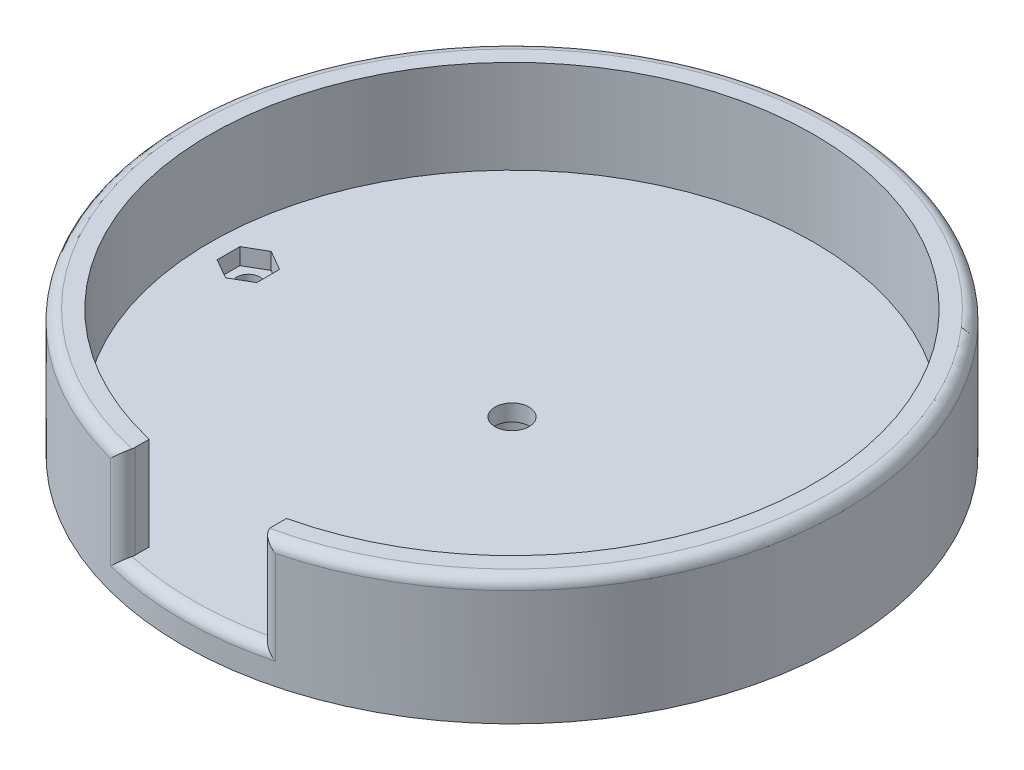
SolidWorks part; units mm, degrees
material "PLA"
ref_plane "Front Plane" through (0, 0, 0) normal (0, 0, 1) x (1, 0, 0)
ref_plane "Top Plane" through (0, 0, 0) normal (0, 1, 0) x (1, 0, 0)
ref_plane "Right Plane" through (0, 0, 0) normal (1, 0, 0) x (0, 0, -1)
sketch "Sketch1" plane through (0, 0, 0) normal (0, 1, 0) x (1, 0, 0)
  line L0 (0, 0) -> (0, -31618.1629) construction
  circle A0 centre (0, 0) radius 60
  circle A1 centre (-48, 0) radius 2.1
  circle A2 centre (0, 0) radius 3.1
  circle A3 centre (48, 0) radius 2.1
  point P6 (0, 0)
  dimension "D1" = 6.2
  dimension "D2" = 4.2
  dimension "D4" = 120
  dimension "D3" = 48
extrude "Boss-Extrude1" add sketch "Sketch1" along normal blind 6
sketch "Sketch2" plane through (0, 6, 0) normal (0, 1, 0) x (1, 0, 0)
  line L0 (0, 0) -> (0, 50000) construction
  line L1 (-51.6, 2.0785) -> (-51.6, -2.0785)
  line L2 (-51.6, -2.0785) -> (-48, -4.1569)
  line L3 (-48, -4.1569) -> (-44.4, -2.0785)
  line L4 (-44.4, -2.0785) -> (-44.4, 2.0785)
  line L5 (-44.4, 2.0785) -> (-48, 4.1569)
  line L6 (-48, 4.1569) -> (-51.6, 2.0785)
  line L7 (48, 4.1569) -> (51.6, 2.0785)
  line L8 (44.4, 2.0785) -> (48, 4.1569)
  line L9 (44.4, -2.0785) -> (44.4, 2.0785)
  line L10 (48, -4.1569) -> (44.4, -2.0785)
  line L11 (51.6, -2.0785) -> (48, -4.1569)
  line L12 (51.6, 2.0785) -> (51.6, -2.0785)
  circle A0 centre (-48, 0) radius 3.6 construction
  circle A1 centre (48, 0) radius 3.6 construction
  point P1 (-51.6, 0)
  dimension "D1" = 7.2
extrude "Cut-Extrude1" cut sketch "Sketch2" against normal blind 3
sketch "Sketch3" plane through (0, 0, 0) normal (0, -1, 0) x (1, 0, 0)
  circle A0 centre (0, 0) radius 4.8
  dimension "D1" = 9.6
extrude "Cut-Extrude2" cut sketch "Sketch3" against normal blind 3
sketch "Sketch4" plane through (0, 6, 0) normal (0, 1, 0) x (1, 0, 0)
  circle A0 centre (0, 0) radius 60
  circle A1 centre (0, 0) radius 55
  dimension "D1" = 120
  dimension "D2" = 5
extrude "Boss-Extrude2" add sketch "Sketch4" along normal blind 17
sketch "Sketch5" plane through (0, 6, 0) normal (0, 1, 0) x (1, 0, 0)
  line L1 (12.5, -67.5) -> (-12.5, -67.5)
  line L2 (12.5, -67.5) -> (12.5, -32.5)
  line L3 (12.5, -32.5) -> (-12.5, -32.5)
  line L4 (-12.5, -67.5) -> (-12.5, -32.5)
  line L5 (12.5, -67.5) -> (-12.5, -32.5) construction
  line L6 (12.5, -32.5) -> (-12.5, -67.5) construction
  point P0 (0, -50)
  point P5 (0, 0)
  dimension "D1" = 50
  dimension "D2" = 25
  dimension "D3" = 35
extrude "Cut-Extrude3" cut sketch "Sketch5" along normal through all
fillet "Fillet1" radius 2 4 edges at (0, 23, -60) (12.5, 14.5, 58.6835) (-12.5, 14.5, 58.6835) (0, 6, 60)
